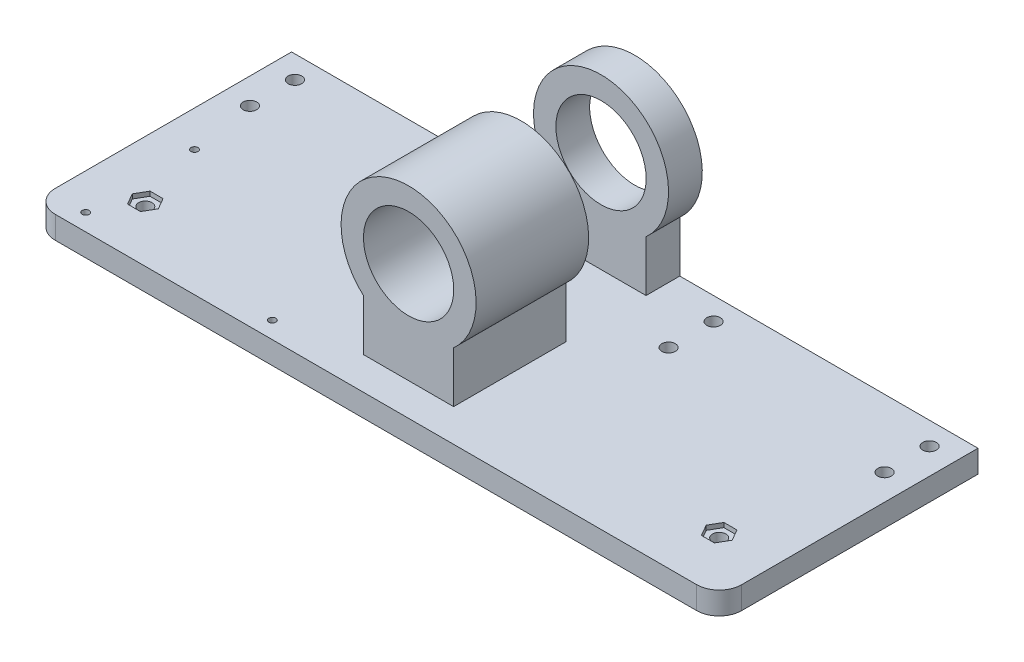
SolidWorks part; units mm, degrees
ref_plane "Front Plane" through (0, 0, 0) normal (0, 0, 1) x (1, 0, 0)
ref_plane "Top Plane" through (0, 0, 0) normal (0, 1, 0) x (1, 0, 0)
ref_plane "Right Plane" through (0, 0, 0) normal (1, 0, 0) x (0, 0, -1)
sketch "Sketch1" plane through (0, 0, 0) normal (0, 1, 0) x (1, 0, 0)
  line L0 (152.5, 115) -> (152.5, 0) construction
  line L1 (0, 0) -> (305, 0)
  line L2 (0, 0) -> (0, 115)
  line L3 (0, 115) -> (305, 115)
  line L4 (305, 0) -> (305, 115)
  line L5 (25, 90) -> (280, 90) construction
  line L6 (280, 25) -> (280, 90) construction
  line L7 (25, 25) -> (280, 25) construction
  line L8 (25, 25) -> (25, 90) construction
  line L9 (152.5, 57.5) -> (25, 57.5) construction
  line L10 (30.7735, 90) -> (27.8868, 95) construction
  line L11 (27.8868, 95) -> (22.1132, 95) construction
  line L12 (22.1132, 95) -> (19.2265, 90) construction
  line L13 (19.2265, 90) -> (22.1132, 85) construction
  line L14 (22.1132, 85) -> (27.8868, 85) construction
  line L15 (27.8868, 85) -> (30.7735, 90) construction
  line L16 (27.8868, 30) -> (30.7735, 25) construction
  line L17 (22.1132, 30) -> (27.8868, 30) construction
  line L18 (19.2265, 25) -> (22.1132, 30) construction
  line L19 (22.1132, 20) -> (19.2265, 25) construction
  line L20 (27.8868, 20) -> (22.1132, 20) construction
  line L21 (30.7735, 25) -> (27.8868, 20) construction
  line L22 (282.8868, 30) -> (277.1132, 30) construction
  line L23 (285.7735, 25) -> (282.8868, 30) construction
  line L24 (282.8868, 20) -> (285.7735, 25) construction
  line L25 (277.1132, 20) -> (282.8868, 20) construction
  line L26 (274.2265, 25) -> (277.1132, 20) construction
  line L27 (277.1132, 30) -> (274.2265, 25) construction
  line L28 (277.1132, 85) -> (274.2265, 90) construction
  line L29 (282.8868, 85) -> (277.1132, 85) construction
  line L30 (285.7735, 90) -> (282.8868, 85) construction
  line L31 (282.8868, 95) -> (285.7735, 90) construction
  line L32 (277.1132, 95) -> (282.8868, 95) construction
  line L33 (274.2265, 90) -> (277.1132, 95) construction
  line L34 (107.5, 105) -> (107.5, 115) construction
  line L35 (132.5, 0) -> (172.5, 0) construction
  line L37 (132.5, 115) -> (172.5, 115) construction
  line L41 (132.5, 25) -> (172.5, 25) construction
  line L50 (305, 14.5) -> (253.3, 14.5) construction
  line L51 (30.7735, 90) -> (22.1132, 95) construction
  line L54 (0, 115) -> (90.0836, 115) construction
  line L55 (0, 115) -> (0, 84.5) construction
  line L62 (0, 84.5) -> (0, 69.5) construction
  line L64 (62, 0) -> (62, 115) construction
  line L65 (253.3, 14.5) -> (253.3, 0) construction
  line L67 (253.3, 14.5) -> (280.2, 14.5) construction
  circle A1 centre (25, 90) radius 5 construction
  circle A3 centre (280, 25) radius 3
  circle A4 centre (25, 25) radius 3
  circle A18 centre (107.5, 105) radius 3
  circle A20 centre (107.5, 85) radius 3
  circle A23 centre (197.5, 105) radius 3
  circle A24 centre (197.5, 85) radius 3
  circle A27 centre (107.5, 65) radius 3 [skipped]
  circle A28 centre (107.5, 45) radius 3 [skipped]
  circle A29 centre (11.5, 85) radius 3
  circle A30 centre (11.5, 105) radius 3
  circle A31 centre (293.5, 105) radius 3
  circle A32 centre (293.5, 85) radius 3
  dimension "D3" = 6
  dimension "D1" = 305
  dimension "D2" = 115
  dimension "D5" = 10
  dimension "D6" = 40
  dimension "D15" = 62
  dimension "D18" = 51.7
  dimension "D19" = 14.5
  dimension "D20" = 26.9
  dimension "D8" = 20
  dimension "D9" = 45
  dimension "D11" = 11.5
  dimension "D4" = 25
  dimension "D14" = 2
  dimension "D7" = 4
  dimension "D10" = 2
extrude "Boss-Extrude1" add sketch "Sketch1" along normal blind 10
sketch "Sketch7" plane through (0, 10, 0) normal (0, 1, 0) x (1, 0, 0)
  line L0 (0, 0) -> (305, 0) construction
  line L1 (132.5, 14.5) -> (172.5, 14.5)
  line L2 (132.5, 14.5) -> (132.5, 64.5)
  line L3 (132.5, 64.5) -> (172.5, 64.5)
  line L4 (172.5, 14.5) -> (172.5, 64.5)
  line L5 (152.5, 0) -> (152.5, 115) construction
  line L6 (305, 115) -> (0, 115) construction
  line L18 (132.5, 100) -> (172.5, 100)
  line L19 (132.5, 100) -> (132.5, 115)
  line L20 (132.5, 115) -> (172.5, 115)
  line L21 (172.5, 100) -> (172.5, 115)
  point P11 (152.5, 64.5)
  point P20 (152.5, 100)
  dimension "D1" = 40
  dimension "D2" = 50
  dimension "D4" = 15
  dimension "D3" = 35.5
extrude "Boss-Extrude2" add sketch "Sketch7" along normal blind 22.6393
sketch "Sketch11" plane through (0, 0, -14.5) normal (0, 0, 1) x (1, 0, 0)
  circle A0 centre (152.5, 55) radius 30
  circle A1 centre (152.5, 55) radius 20.05
  dimension "D1" = 60
  dimension "D2" = 40.1
extrude "Boss-Extrude3" add sketch "Sketch11" against normal up to surface (100.5 mm away) up to face at (152.5, 13.1598, -115)
ref_plane "Plane1" through (0, 0, -57.5) normal (0, 0, 1) x (1, 0, 0)
sketch "Sketch12" plane through (305, 0, 0) normal (1, 0, 0) x (0, 0, -1)
  line L0 (115, 85) -> (14.5, 85) construction
  line L1 (64.5, 10) -> (100, 10)
  line L2 (64.5, 10) -> (64.5, 85)
  line L3 (64.5, 85) -> (100, 85)
  line L4 (100, 10) -> (100, 85)
  line L6 (100, 32.6393) -> (100, 10) construction
extrude "Cut-Extrude2" cut sketch "Sketch12" against normal through all
sketch "Sketch6" plane through (0, 10, 0) normal (0, 1, 0) x (1, 0, 0)
  line L0 (152.5, 115) -> (152.5, 0) construction
  line L8 (0, 0) -> (305, 0) construction
  line L9 (152.5, 57.5) -> (0, 57.5) construction
  line L10 (0, 115) -> (0, 0) construction
  line L29 (27.8868, 30) -> (30.7735, 25)
  line L30 (274.2265, 25) -> (277.1132, 20)
  line L31 (277.1132, 20) -> (282.8868, 20)
  line L32 (282.8868, 20) -> (285.7735, 25)
  line L33 (285.7735, 25) -> (282.8868, 30)
  line L34 (282.8868, 30) -> (277.1132, 30)
  line L35 (277.1132, 30) -> (274.2265, 25)
  line L36 (22.1132, 30) -> (27.8868, 30)
  line L37 (19.2265, 25) -> (22.1132, 30)
  line L38 (22.1132, 20) -> (19.2265, 25)
  line L39 (27.8868, 20) -> (22.1132, 20)
  line L40 (30.7735, 25) -> (27.8868, 20)
  circle A0 centre (280, 25) radius 5 construction
  dimension "D1" = 10
extrude "Cut-Extrude1" cut sketch "Sketch6" against normal blind 2
sketch "Sketch16" plane through (0, 10, 0) normal (0, 1, 0) x (1, 0, 0)
  line L0 (0, 0) -> (305, 0) construction
  line L1 (0, 115) -> (0, 0) construction
  circle A0 centre (16, 7.5) radius 1.55
  circle A1 centre (98.95, 7.5) radius 1.55
  circle A2 centre (16, 55.866) radius 1.55
  circle A3 centre (91.33, 55.866) radius 1.55
  dimension "D1" = 3.1
  dimension "D2" = 7.5
  dimension "D3" = 82.95
  dimension "D4" = 16
  dimension "D5" = 48.366
  dimension "D6" = 75.33
extrude "Cut-Extrude3" cut sketch "Sketch16" against normal through all
fillet "Fillet3" radius 10 2 edges at (305, 5, 0) (0, 5, 0)
chamfer "Chamfer2" distance 1.65 4 edges at (98.95, 0, -5.95) (91.33, 0, -54.316) (16, 0, -5.95) (16, 0, -54.316)
equation "\"joint_width\"=4"
equation "\"short_base_length\"=11.5"
equation "\"D2@Sketch1\"=\"short_base_length\""
equation "\"outer_diam_main_joint\"=6"
equation "\"D1@Sketch11\"=\"outer_diam_main_joint\""
equation "\"D1@Sketch7\"=\"outer_diam_main_joint\"-2"
equation "\"D1@Boss-Extrude2\"=(\"outer_diam_main_joint\"/2)+1.5cm-sqr((\"outer_diam_main_joint\"/2)^2-((\"outer_diam_main_joint\"-2)/2)^2)"
equation "\"D6@Sketch1\"=\"outer_diam_main_joint\"-2"
equation "\"pulleyside\"=1.5"
